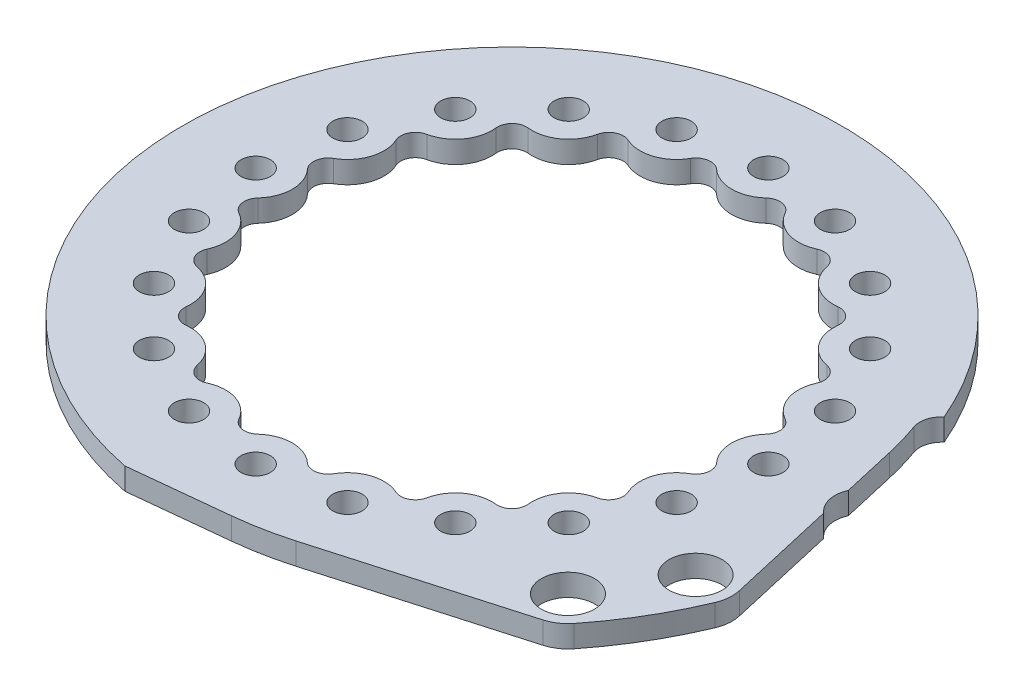
SolidWorks part; units mm, degrees
material "POM Acetal Copolymer"
ref_plane "Front Plane" through (0, 0, 0) normal (0, 0, 1) x (1, 0, 0)
ref_plane "Top Plane" through (0, 0, 0) normal (0, 1, 0) x (1, 0, 0)
ref_plane "Right Plane" through (0, 0, 0) normal (1, 0, 0) x (0, 0, -1)
sketch "Sketch1" plane through (0, 0, 0) normal (0, 1, 0) x (1, 0, 0)
  circle A0 centre (0, 0) radius 60
  circle A1 centre (0, 0) radius 103.5
  dimension "D1" = 120
  dimension "D2" = 207
extrude "Boss-Extrude1" add sketch "Sketch1" along normal blind 6
sketch "Sketch2" plane through (0, 6, 0) normal (0, 1, 0) x (1, 0, 0)
  circle A0 centre (0, 70) radius 4
  circle A1 centre (0, 0) radius 70 construction
  dimension "D1" = 140
  dimension "D2" = 8
extrude "Cut-Extrude1" cut sketch "Sketch2" against normal through all
pattern_circular "CirPattern1" count 20 over 360 about axis through (0, 6, 0) along (0, -1, 0) of "Cut-Extrude1"
sketch "Sketch3" plane through (0, 6, 0) normal (0, 1, 0) x (1, 0, 0)
  line L0 (0, 0) -> (79.7975, -47.0982) construction
  line L1 (0, 0) -> (87.353, 0) construction
  line L2 (86.267, -36.1371) -> (108.1892, -49.076) construction
  line L3 (73.328, -58.0593) -> (86.267, -36.1371) construction
  line L4 (108.1892, -49.076) -> (95.2502, -70.9982) construction
  line L5 (95.2502, -70.9982) -> (73.328, -58.0593) construction
  circle A0 centre (86.267, -36.1371) radius 7.25
  circle A1 centre (73.328, -58.0593) radius 7.25
  dimension "D1" = 14.5
  dimension "D2" = 92.66
  dimension "D3" = 25.4558
  dimension "D4" = 30.55
extrude "Cut-Extrude2" cut sketch "Sketch3" against normal blind 6
sketch "Sketch4" plane through (0, 6, 0) normal (0, 1, 0) x (1, 0, 0)
  line L0 (23.7169, -82.665) -> (76.0775, -67.6426)
  line L1 (83.8323, 19.1872) -> (95.9856, -33.9127)
  arc A1 (76.0775, -67.6426) -> (81.1445, -64.2481) centre (73.328, -58.0593) ccw
  arc A2 (95.4627, -39.9891) -> (95.9856, -33.9127) centre (86.267, -36.1371) ccw
  circle A3 centre (0, 0) radius 103.5 construction
  arc A4 (83.8323, 19.1872) -> (23.7169, -82.665) centre (0, 0) ccw
  arc A5 (81.1445, -64.2481) -> (95.4627, -39.9891) centre (0, 0) ccw
  dimension "D1" = 86
extrude "Cut-Extrude3" cut sketch "Sketch4" against normal through all flip side to cut
sketch "Sketch5" plane through (0, 6, 0) normal (0, 1, 0) x (1, 0, 0)
  arc A40 (46.6947, 42.27) -> (54.6307, 31.3471) centre (56.6312, 41.145) ccw
  arc A41 (57.4714, 25.7718) -> (54.6307, 31.3471) centre (53.8304, 27.428) ccw
  arc A42 (57.4714, 25.7718) -> (61.6436, 12.9311) centre (66.574, 21.6312) ccw
  arc A43 (62.6225, 6.7507) -> (61.6436, 12.9311) centre (59.6715, 9.451) ccw
  arc A44 (62.6225, 6.7507) -> (62.6225, -6.7507) centre (70, 0) ccw
  arc A45 (61.6436, -12.9311) -> (62.6225, -6.7507) centre (59.6715, -9.451) ccw
  arc A46 (61.6436, -12.9311) -> (57.4714, -25.7718) centre (66.574, -21.6312) ccw
  arc A47 (54.6307, -31.3471) -> (57.4714, -25.7718) centre (53.8304, -27.428) ccw
  arc A48 (54.6307, -31.3471) -> (46.6947, -42.27) centre (56.6312, -41.145) ccw
  arc A49 (42.27, -46.6947) -> (46.6947, -42.27) centre (42.7201, -42.7201) ccw
  arc A50 (42.27, -46.6947) -> (31.3471, -54.6307) centre (41.145, -56.6312) ccw
  arc A51 (25.7718, -57.4714) -> (31.3471, -54.6307) centre (27.428, -53.8304) ccw
  arc A52 (25.7718, -57.4714) -> (12.9311, -61.6436) centre (21.6312, -66.574) ccw
  arc A53 (6.7507, -62.6225) -> (12.9311, -61.6436) centre (9.451, -59.6715) ccw
  arc A54 (6.7507, -62.6225) -> (-6.7507, -62.6225) centre (0, -70) ccw
  arc A55 (-12.9311, -61.6436) -> (-6.7507, -62.6225) centre (-9.451, -59.6715) ccw
  arc A56 (-12.9311, -61.6436) -> (-25.7718, -57.4714) centre (-21.6312, -66.574) ccw
  arc A57 (-31.3471, -54.6307) -> (-25.7718, -57.4714) centre (-27.428, -53.8304) ccw
  arc A58 (-31.3471, -54.6307) -> (-42.27, -46.6947) centre (-41.145, -56.6312) ccw
  arc A59 (-46.6947, -42.27) -> (-42.27, -46.6947) centre (-42.7201, -42.7201) ccw
  arc A60 (-46.6947, -42.27) -> (-54.6307, -31.3471) centre (-56.6312, -41.145) ccw
  arc A61 (-57.4714, -25.7718) -> (-54.6307, -31.3471) centre (-53.8304, -27.428) ccw
  arc A62 (-57.4714, -25.7718) -> (-61.6436, -12.9311) centre (-66.574, -21.6312) ccw
  arc A63 (-62.6225, -6.7507) -> (-61.6436, -12.9311) centre (-59.6715, -9.451) ccw
  arc A64 (-62.6225, -6.7507) -> (-62.6225, 6.7507) centre (-70, 0) ccw
  arc A65 (-61.6436, 12.9311) -> (-62.6225, 6.7507) centre (-59.6715, 9.451) ccw
  arc A66 (-61.6436, 12.9311) -> (-57.4714, 25.7718) centre (-66.574, 21.6312) ccw
  arc A67 (-54.6307, 31.3471) -> (-57.4714, 25.7718) centre (-53.8304, 27.428) ccw
  arc A68 (-54.6307, 31.3471) -> (-46.6947, 42.27) centre (-56.6312, 41.145) ccw
  arc A69 (-42.27, 46.6947) -> (-46.6947, 42.27) centre (-42.7201, 42.7201) ccw
  arc A70 (-42.27, 46.6947) -> (-31.3471, 54.6307) centre (-41.145, 56.6312) ccw
  arc A71 (-25.7718, 57.4714) -> (-31.3471, 54.6307) centre (-27.428, 53.8304) ccw
  arc A72 (-25.7718, 57.4714) -> (-12.9311, 61.6436) centre (-21.6312, 66.574) ccw
  arc A73 (-6.7507, 62.6225) -> (-12.9311, 61.6436) centre (-9.451, 59.6715) ccw
  arc A74 (-6.7507, 62.6225) -> (6.7507, 62.6225) centre (0, 70) ccw
  arc A75 (12.9311, 61.6436) -> (6.7507, 62.6225) centre (9.451, 59.6715) ccw
  arc A76 (12.9311, 61.6436) -> (25.7718, 57.4714) centre (21.6312, 66.574) ccw
  arc A77 (31.3471, 54.6307) -> (25.7718, 57.4714) centre (27.428, 53.8304) ccw
  arc A78 (31.3471, 54.6307) -> (42.27, 46.6947) centre (41.145, 56.6312) ccw
  arc A79 (46.6947, 42.27) -> (42.27, 46.6947) centre (42.7201, 42.7201) ccw
extrude "Cut-Extrude4" cut sketch "Sketch5" against normal blind 10
sketch "Sketch6" plane through (0, 0, 0) normal (0, -1, 0) x (1, 0, 0)
  line L4 (8.9894, 85.5289) -> (-17.3982, 88.3023)
  line L5 (82.8454, -35.1658) -> (79.1634, -33.6029)
  arc A0 (23.7169, 82.665) -> (83.8323, -19.1872) centre (0, 0) ccw construction
  arc A4 (8.9894, 85.5289) -> (79.1634, -33.6029) centre (0, 0) ccw
  arc A5 (-17.3982, 88.3023) -> (82.8454, -35.1658) centre (0, 0) ccw
  dimension "D1" = 90
extrude "Boss-Extrude2" add sketch "Sketch6" against normal up to surface (6 mm away) up to face at (73.328, 6, 65.3093)
fillet "Fillet1" radius 6 1 edges at (79.1634, 3, -33.6029)
sketch "Sketch7" plane through (0, 0, 0) normal (0, -1, 0) x (1, 0, 0)
  circle A0 centre (94.0024, -1.6864) radius 7.5
  dimension "D1" = 15
extrude "Cut-Extrude5" cut sketch "Sketch7" against normal blind 10
